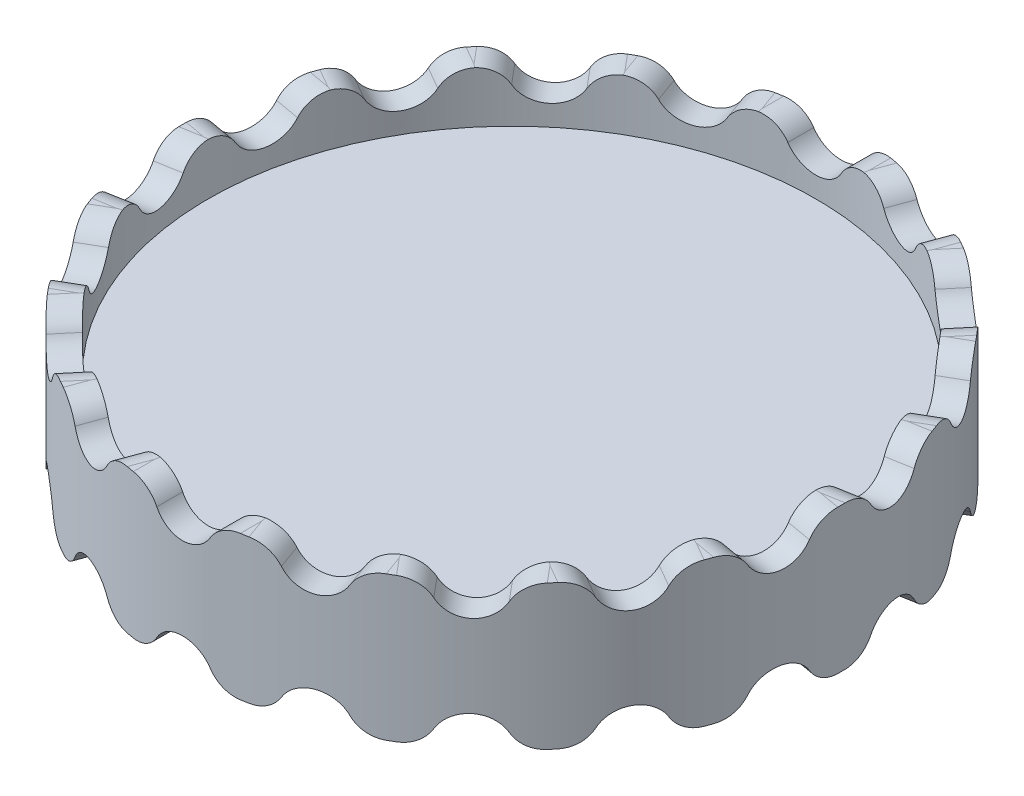
SolidWorks part; units mm, degrees
ref_plane "Front Plane" through (0, 0, 0) normal (0, 0, 1) x (1, 0, 0)
ref_plane "Top Plane" through (0, 0, 0) normal (0, 1, 0) x (1, 0, 0)
ref_plane "Right Plane" through (0, 0, 0) normal (1, 0, 0) x (0, 0, -1)
sketch "Sketch1" plane through (0, 0, 0) normal (0, 1, 0) x (1, 0, 0)
  circle A0 centre (0, 0) radius 16
  dimension "D1" = 32
extrude "Boss-Extrude1" add sketch "Sketch1" along normal blind 7 contours A0
sketch "Sketch2" plane through (0, 7, 0) normal (0, 1, 0) x (1, 0, 0)
  line L0 (0, 0) -> (0, -16) construction
  circle A0 centre (0, 0) radius 16 construction
ref_plane "Plane1" through (0, 7, 16) normal (0, 0, 1) x (1, 0, 0)
sketch "Sketch4" plane through (0, 7, 0) normal (0, 1, 0) x (1, 0, 0)
  circle A0 centre (0, 0) radius 14.75
  dimension "D1" = 29.5
extrude "Cut-Extrude1" cut sketch "Sketch4" against normal blind 2.5
sketch "Sketch6" plane through (0, 7, 16) normal (0, 0, 1) x (1, 0, 0)
  line L0 (0, 0) -> (0, -7) construction
  line L1 (14.75, 0) -> (-14.75, 0) construction
  point P5 (0, -3.5)
ref_plane "Plane2" through (0, 3.5, 0) normal (0, 1, 0) x (1, 0, 0)
mirror "Mirror1" about plane through (0, 3.5, 0) normal (0, 1, 0) of "Cut-Extrude1"
sketch "Sketch3" plane through (0, 7, 16) normal (0, 0, 1) x (1, 0, 0)
  line L0 (0, 0) -> (0, -1.5) construction
  line L1 (0, -7) -> (0, -5.5) construction
  line L2 (1.5, -7) -> (-1.5, -7)
  line L3 (-16, -7) -> (16, -7) construction
  line L4 (-1.5, -7) -> (0, -7) construction
  line L5 (0, -7) -> (1.5, -7) construction
  line L6 (-1.5, 0) -> (1.5, 0)
  line L7 (16, 0) -> (-16, 0) construction
  line L8 (-1.5, 0) -> (0, 0) construction
  line L9 (0, 0) -> (1.5, 0) construction
  arc A0 (1.5, -7) -> (-1.5, -7) centre (0, -7) ccw
  arc A1 (-1.5, 0) -> (1.5, 0) centre (0, 0) ccw
  point P5 (0, -7)
  point P6 (0, 0)
  dimension "D1" = 1.5
  dimension "D2" = 1.5
  dimension "D3" = 3
extrude "Cut-Extrude2" cut sketch "Sketch3" against normal up to surface (1.3265 mm away) up to face at (0, 4.5, 14.75)
fillet "Fillet1" radius 1.5 4 edges at (1.5, 7, 15.3015) (-1.5, 7, 15.3015) (1.5, 0, 15.3015) (-1.5, 0, 15.3015)
pattern_circular "CirPattern1" count 18 over 360 about axis through (0, 7, 0) along (0, -1, 0) of "Cut-Extrude2", "Fillet1"
equation "\"board_length\"= 260mm"
equation "\"board_height\"= 200mm"
equation "\"board_width\"= 16.5mm"
equation "\"token_thickness\"= 7mm"
equation "\"token_diameter\"= 32mm"
equation "\"board_side_lower_height\"= 55mm"
equation "\"board_side_height\"= 156.5mm"
equation "\"board_side_length\"= 100mm"
equation "\"board_slot_width\"= \"board_length\" / 7"
equation "\"token_ridge\"= ( \"token_thickness\" - 4mm ) / 2"
equation "\"D1@Sketch1\"=\"token_diameter\""
equation "\"D1@Boss-Extrude1\"=\"token_thickness\""
equation "\"D1@Sketch3\"=\"token_ridge\""
equation "\"D2@Sketch3\"=\"token_ridge\""
equation "\"token_ridge_width\"= 1.5mm"
equation "\"D3@Sketch3\"=\"token_ridge_width\"*2"
equation "\"D1@Sketch4\"=\"token_diameter\"-2.5mm"
equation "\"D1@Cut-Extrude1\"=\"token_ridge\""
equation "\"D1@Fillet1\"=\"token_ridge_width\""
